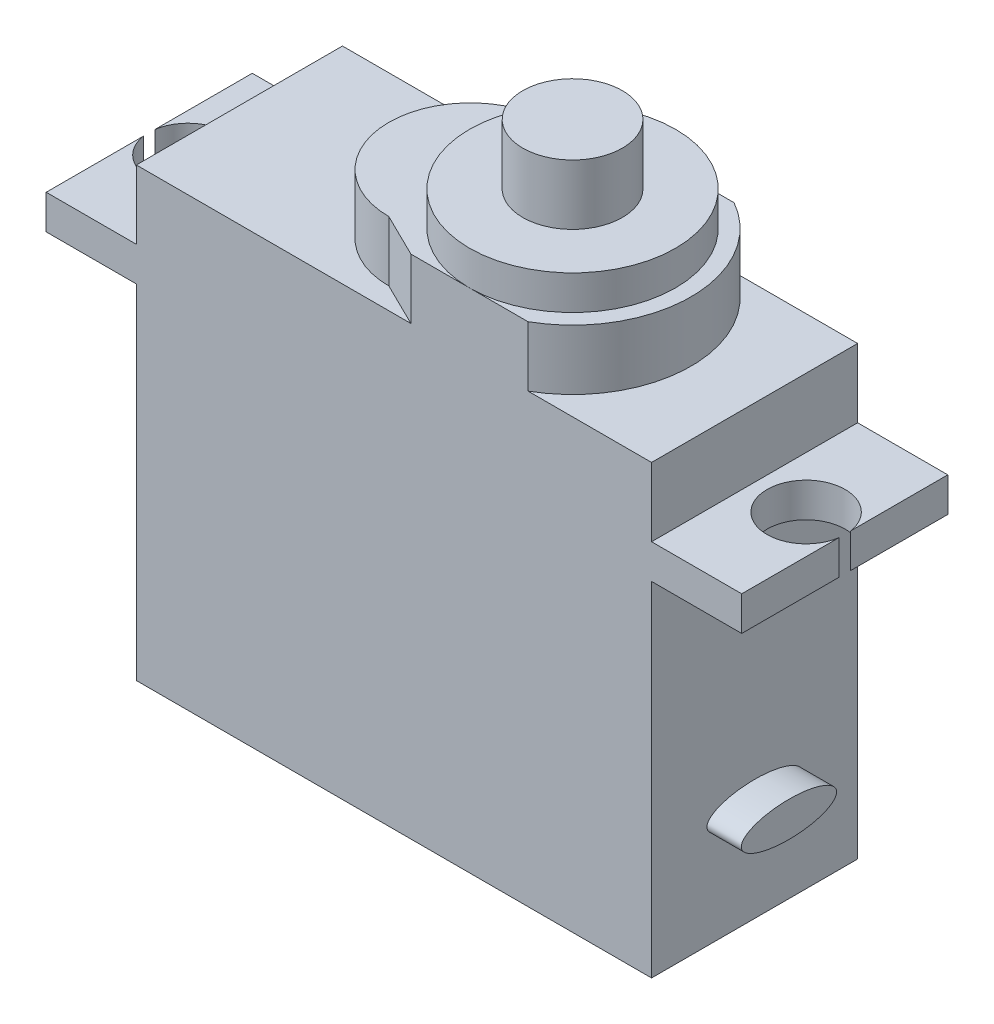
SolidWorks part; units mm, degrees
ref_plane "Front Plane" through (0, 0, 0) normal (0, 0, 1) x (1, 0, 0)
ref_plane "Top Plane" through (0, 0, 0) normal (0, 1, 0) x (1, 0, 0)
ref_plane "Right Plane" through (0, 0, 0) normal (1, 0, 0) x (0, 0, -1)
sketch "Sketch1" plane through (0, 0, 0) normal (0, 0, 1) x (1, 0, 0)
  line L0 (0, 22) -> (0, 26)
  line L1 (0, 0) -> (30, 0)
  line L2 (0, 0) -> (0, 20)
  line L3 (0, 26) -> (8.7, 26)
  line L4 (30, 0) -> (30, 20)
  line L5 (0, 20) -> (-5.25, 20)
  line L7 (0, 22) -> (-5.25, 22)
  line L8 (-5.25, 20) -> (-5.25, 22)
  line L9 (30, 22) -> (35.25, 22)
  line L11 (30, 20) -> (35.25, 20)
  line L12 (35.25, 22) -> (35.25, 20)
  line L14 (8.7, 26) -> (8.7, 31.5)
  line L15 (8.7, 31.5) -> (26.3, 31.5)
  line L16 (26.3, 26) -> (26.3, 31.5)
  line L17 (26.3, 26) -> (30, 26)
  line L18 (30, 22) -> (30, 26)
  dimension "D1" = 26
  dimension "D2" = 30
  dimension "D3" = 40.5
  dimension "D4" = 5.25
  dimension "D5" = 17.6
  dimension "D6" = 3.7
  dimension "D7" = 2
  dimension "D8" = 2
  dimension "D9" = 4
  dimension "D10" = 4
  dimension "D11" = 5.5
extrude "Boss-Extrude1" add sketch "Sketch1" along normal blind 12
sketch "Sketch2" plane through (30, 0, 0) normal (1, 0, 0) x (0, 0, -1)
  line L0 (-6, 0) -> (-6, 15.9568) construction
  line L1 (-12, 0) -> (0, 0) construction
  ellipse E0 centre (-6, 6) end of major axis (-3.2234, 6) minor radius 1.0178
  dimension "D1" = 6
extrude "Boss-Extrude2" add sketch "Sketch2" along normal blind 2
sketch "Sketch3" plane through (0, 22, 0) normal (0, 1, 0) x (1, 0, 0)
  line L0 (0, 0) -> (-5.25, 0) construction
  line L1 (35.25, 0) -> (30, 0) construction
  line L5 (0, -12) -> (0, 0) construction
  circle A0 centre (-3, -6) radius 2.275
  circle A1 centre (33, -6) radius 2.275
  dimension "D3" = 4.55
  dimension "D4" = 4.55
  dimension "D1" = 6
  dimension "D2" = 6
  dimension "D5" = 36
  dimension "D6" = 3
extrude "Cut-Extrude3" cut sketch "Sketch3" against normal blind 2
sketch "Sketch5" plane through (0, 31.5, 0) normal (0, 1, 0) x (1, 0, 0)
  line L0 (26.3, -12) -> (8.7, -12) construction
  line L1 (30, -12) -> (30, 0) construction
  line L3 (22.8073, 0) -> (26.3, 0)
  line L4 (26.3, 0) -> (26.3, -6)
  line L6 (26.3, 0) -> (8.7, 0) construction
  line L9 (26.3, -6) -> (26.3, -12)
  line L10 (26.3, -12) -> (22.8073, -12)
  circle A0 centre (19.4, -6) radius 2.9
  arc A2 (22.8073, -12) -> (22.8073, 0) centre (19.4, -6) ccw
  line M7 (26.3, 0) -> (8.7, 0)
  line M9 (8.7, -12) -> (26.3, -12)
  line M10 (26.3, -12) -> (26.3, 0)
  dimension "D1" = 5.8
  dimension "D2" = 6
  dimension "D3" = 10.6
extrude "Boss-Extrude3" add sketch "Sketch5" along normal blind 3.5 contours A0 region at (19.4, 31.5, 6)
extrude "Cut-Extrude4" cut sketch "Sketch5<3>" against normal up to surface (5.5 mm away) contours A2 M10 M7 | A2 M9 M10 region at (25.3212, 31.5, 10.5862) region at (25.3212, 31.5, 1.4138) up to face at (28.15, 26, 6)
sketch "Sketch5<3>" plane through (0, 31.5, 0) normal (0, 1, 0) x (1, 0, 0) same geometry as "Sketch5"
sketch "Sketch7" plane through (0, 31.5, 0) normal (0, 1, 0) x (1, 0, 0)
  line L0 (22.8073, 0) -> (19.4, 0)
  line L1 (19.4, -12) -> (22.8073, -12)
  line L2 (8.7, 0) -> (8.7, -12)
  line L3 (8.7, -12) -> (19.4, -12)
  line L4 (8.7, 0) -> (19.4, 0)
  circle A0 centre (19.4, -6) radius 6
  arc A1 (22.8073, -12) -> (22.8073, 0) centre (19.4, -6) ccw
  line M4 (8.7, -12) -> (22.8073, -12)
  arc M5 (22.8073, -12) -> (22.8073, 0) centre (19.4, -6) ccw
  line M6 (22.8073, 0) -> (8.7, 0)
  line M7 (8.7, 0) -> (8.7, -12)
extrude "Cut-Extrude5" cut sketch "Sketch7" against normal blind 2 contours A0 M4 M5 M6 | A0 M6 M7 M4 region at (26.1616, 31.5, 6) region at (11.8436, 31.5, 6)
sketch "Sketch8" plane through (0, 29.5, 0) normal (0, 1, 0) x (1, 0, 0)
  line L0 (8.7, 0) -> (8.7, -12) construction
  line L1 (19.4, 0) -> (8.7, 0) construction
  line L2 (13.45, -10.75) -> (16.0176, -12.0141)
  line L3 (13.45, -1.25) -> (15.9927, 0)
  line L4 (15.9927, 0) -> (8.7, 0)
  line L5 (8.7, 0) -> (8.7, -12)
  line L6 (8.7, -12) -> (16.0176, -12.0141)
  arc A0 (13.45, -1.25) -> (13.45, -10.75) centre (13.45, -6) ccw
  circle A1 centre (19.4, -6) radius 6.9 construction
  line M4 (19.4, 0) -> (8.7, 0)
  line M5 (8.7, 0) -> (8.7, -12)
  line M6 (8.7, -12) -> (19.4, -12)
  dimension "D1" = 9.5
  dimension "D2" = 4.75
  dimension "D3" = 6
extrude "Cut-Extrude6" cut sketch "Sketch8" against normal up to surface (3.5 mm away) contours A0 L3 M4 M5 | A0 L5 L2 M6 region at (10.9746, 29.5, 1.2583) region at (10.9739, 29.5, 10.7416) up to face at (4.35, 26, 6)
